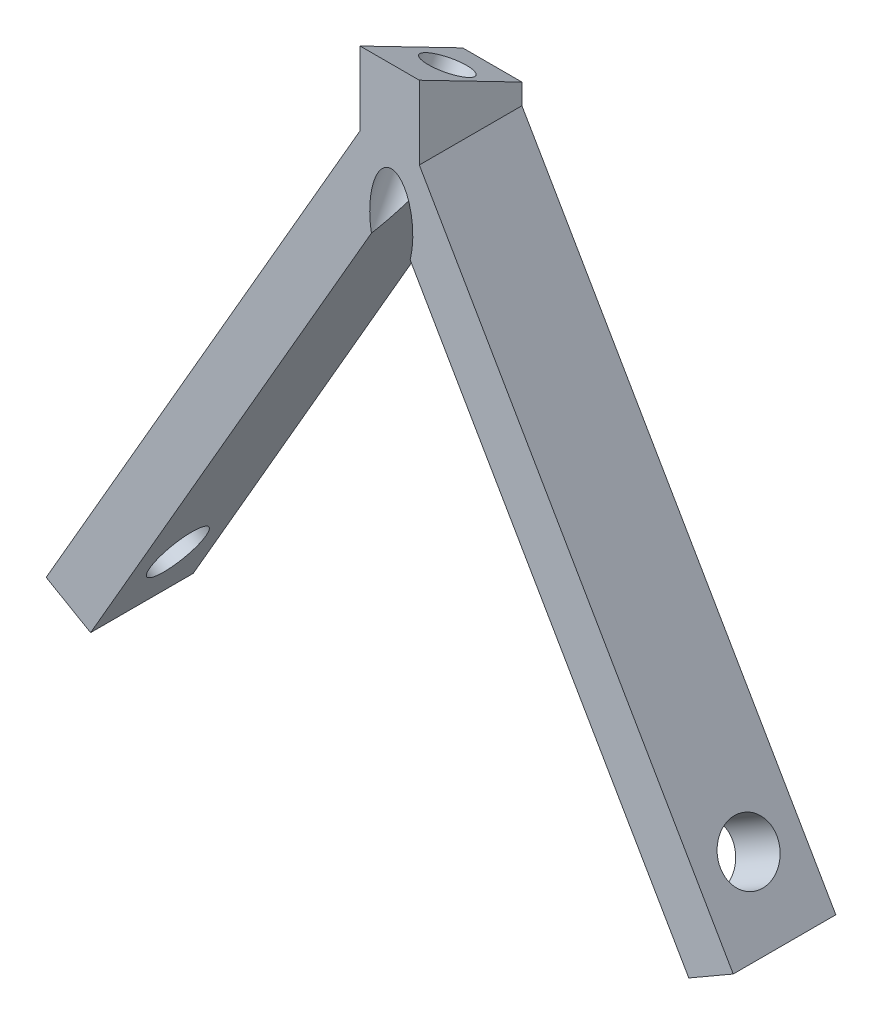
SolidWorks part; units mm, degrees
ref_plane "Top" through (0, 0, 0) normal (0, 0, 1) x (1, 0, 0)
ref_plane "Front" through (0, 0, 0) normal (0, 1, 0) x (1, 0, 0)
ref_plane "Right" through (0, 0, 0) normal (1, 0, 0) x (0, 0, -1)
sketch "Sketch1" plane through (0, 0, 0) normal (0, 0, 1) x (1, 0, 0)
  line L0 (-2.8868, 0) -> (2.8868, 0)
  line L1 (2.8868, 0) -> (33.4801, -52.9893)
  line L2 (33.4801, -52.9893) -> (29.15, -55.4893)
  line L3 (29.15, -55.4893) -> (0, -5)
  line L4 (0, -5) -> (-29.15, -55.4893)
  line L5 (-29.15, -55.4893) -> (-33.4801, -52.9893)
  line L6 (-33.4801, -52.9893) -> (-2.8868, 0)
  point P3 (0, 0)
  point P9 (0, 0)
  point P10 (0, -5)
  dimension "D1" = 5
  dimension "D2" = 58.3
  dimension "D3" = 5
  dimension "D4" = 60
extrude "Boss-Extrude1" add sketch "Sketch1" along normal blind 10
sketch "Sketch2" plane through (2.1651, 1.25, 0) normal (0.866, 0.5, 0) x (0, 0, -1)
  line L0 (-10, -62.6301) -> (0, -62.6301) construction
  line L1 (-10, -62.6301) -> (-10, -1.4434) construction
  point P0 (-5, -55.6301)
  dimension "D1" = 7
  dimension "D2" = 5
sketch "Sketch3" plane through (-2.1651, 1.25, 0) normal (-0.866, 0.5, 0) x (0, 0, 1)
  line L0 (0, -1.4434) -> (0, -62.6301) construction
  line L1 (10, -62.6301) -> (0, -62.6301) construction
  point P0 (5, -55.6301)
  point P3 (0, 0)
  dimension "D1" = 5
  dimension "D2" = 7
hole_wizard "M5 Clearance Hole1" positions "Sketch4" profile "Sketch5" hole size "M5" standard "DIN" end condition through all
sketch "Sketch4" plane through (-2.1651, 1.25, 0) normal (-0.866, 0.5, 0) x (0, 0, 1)
  point P0 (5, -55.6301)
sketch "Sketch5" plane through (-29.9801, -46.9271, 5) normal (0, 0, 1) x (-0.5, -0.866, 0)
  line L0 (0, 0) -> (0, 59.2393)
  line L1 (0, 59.2393) -> (2.75, 59.2393)
  line L2 (2.75, 59.2393) -> (2.75, 0)
  line L5 (2.75, 0) -> (0, 0)
  line L11 (0, -6.35) -> (0, 107.95) construction
  dimension "Thru Hole Dia." = 5.5
  dimension "Thru Hole Depth" = 59.2393
hole_wizard "M5 Clearance Hole2" positions "Sketch6" profile "Sketch7" hole size "M5" standard "DIN" end condition through all
sketch "Sketch6" plane through (2.1651, 1.25, 0) normal (0.866, 0.5, 0) x (0, 0, -1)
  point P0 (-5, -55.6301)
sketch "Sketch7" plane through (29.9801, -46.9271, 5) normal (0, 0, 1) x (-0.5, 0.866, 0)
  line L0 (0, 0) -> (0, 59.2393)
  line L1 (0, 59.2393) -> (2.75, 59.2393)
  line L2 (2.75, 59.2393) -> (2.75, 0)
  line L5 (2.75, 0) -> (0, 0)
  line L11 (0, -6.35) -> (0, 107.95) construction
  dimension "Thru Hole Dia." = 5.5
  dimension "Thru Hole Depth" = 59.2393
sketch "Sketch8" plane through (0, 0, 0) normal (1, 0, 0) x (0, 0, -1)
  line L1 (-10, 7.157) -> (-10, 0)
  line L2 (-10, 0) -> (0, 0)
  line L3 (0, 0) -> (0, 2)
  line L4 (0, 2) -> (-10, 7.157)
  dimension "D1" = 2
  dimension "D2" = 27.28
extrude "Boss-Extrude2" add sketch "Sketch8" along normal up to vertex (2.8868 mm away) and the other way up to vertex (2.8868 mm away) up to point (2.8868, 0, 0) other way up to point (-2.8868, 0, 0)
sketch "Sketch9" plane through (0, 1.5799, -0.8147) normal (0, 0.8888, -0.4583) x (1, 0, 0)
  line L0 (2.8868, -0.9167) -> (-2.8868, -0.9167) construction
  line L3 (-2.8868, -0.9167) -> (-2.8868, -12.1681) construction
  circle A0 centre (0.1541, -6.0167) radius 2.1
  point P0 (0.1541, -6.0167)
  dimension "D3" = 4.2
  dimension "D1" = 5.1
  dimension "D2" = 3.0409
extrude "Cut-Extrude1" cut sketch "Sketch9" against normal through all
